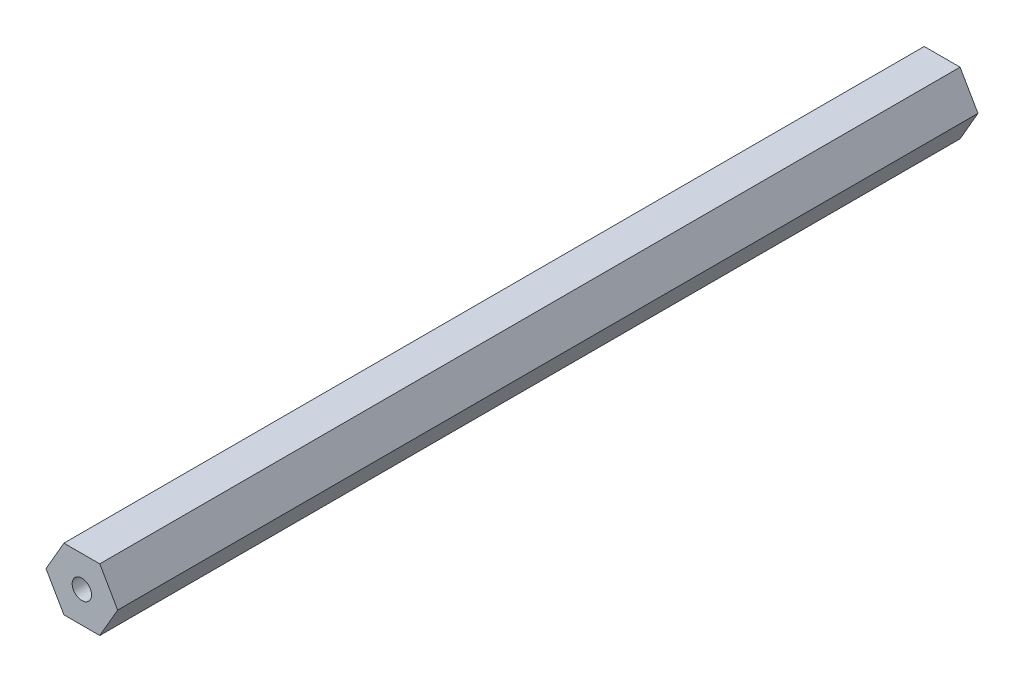
SolidWorks part; units mm, degrees
material "7075-T6 (SN)"
ref_plane "Front Plane" through (0, 0, 0) normal (0, 0, 1) x (1, 0, 0)
ref_plane "Top Plane" through (0, 0, 0) normal (0, 1, 0) x (1, 0, 0)
ref_plane "Right Plane" through (0, 0, 0) normal (1, 0, 0) x (0, 0, -1)
other "Configuration Table"
sketch "Sketch1" plane through (0, 0, 0) normal (0, 0, 1) x (1, 0, 0)
  line L1 (6.35, 0) -> (3.175, 5.4993)
  line L2 (3.175, 5.4993) -> (-3.175, 5.4993)
  line L3 (-3.175, 5.4993) -> (-6.35, 0)
  line L4 (-6.35, 0) -> (-3.175, -5.4993)
  line L5 (-3.175, -5.4993) -> (3.175, -5.4993)
  line L6 (3.175, -5.4993) -> (6.35, 0)
  circle A0 centre (0, 0) radius 5.4993 construction
  circle A1 centre (0, 0) radius 1.7145
  dimension "D2" = 3.429
  dimension "D1" = 12.7
extrude "Boss-Extrude1" add sketch "Sketch1" along normal mid plane 152.4
equation "\"length\"= 6"
equation "\"D1@Boss-Extrude1\"=\"length\""
